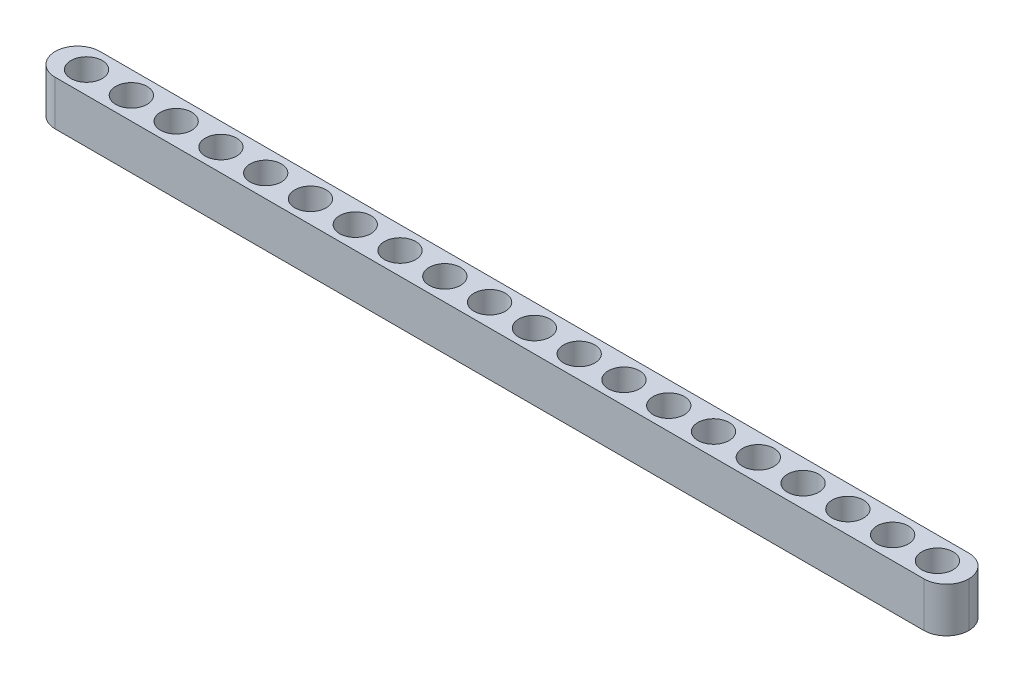
SolidWorks part; units mm, degrees
ref_plane "Front Plane" through (0, 0, 0) normal (0, 0, 1) x (1, 0, 0)
ref_plane "Top Plane" through (0, 0, 0) normal (0, 1, 0) x (1, 0, 0)
ref_plane "Right Plane" through (0, 0, 0) normal (1, 0, 0) x (0, 0, -1)
sketch "Sketch1" plane through (0, 0, 0) normal (1, 0, 0) x (0, 0, -1)
  line L1 (0, 0) -> (10, 0)
  line L2 (0, 0) -> (0, 10)
  line L3 (0, 10) -> (10, 10)
  line L4 (10, 0) -> (10, 10)
extrude "Boss-Extrude1" add sketch "Sketch1" along normal blind 204
sketch "Sketch2" plane through (0, 10, 0) normal (0, 1, 0) x (1, 0, 0)
  line L0 (0, 5) -> (7, 5) construction
  line L1 (0, 10) -> (0, 0) construction
  circle A0 centre (7, 5) radius 3.5
extrude "Cut-Extrude1" cut sketch "Sketch2" against normal blind 10
pattern_linear "LPattern1" count 20 spacing 10 along (1, 0, 0) of "Cut-Extrude1"
fillet "Fillet1" radius 5 4 edges at (0, 5, 0) (0, 5, -10) (204, 5, 0) (204, 5, -10)
